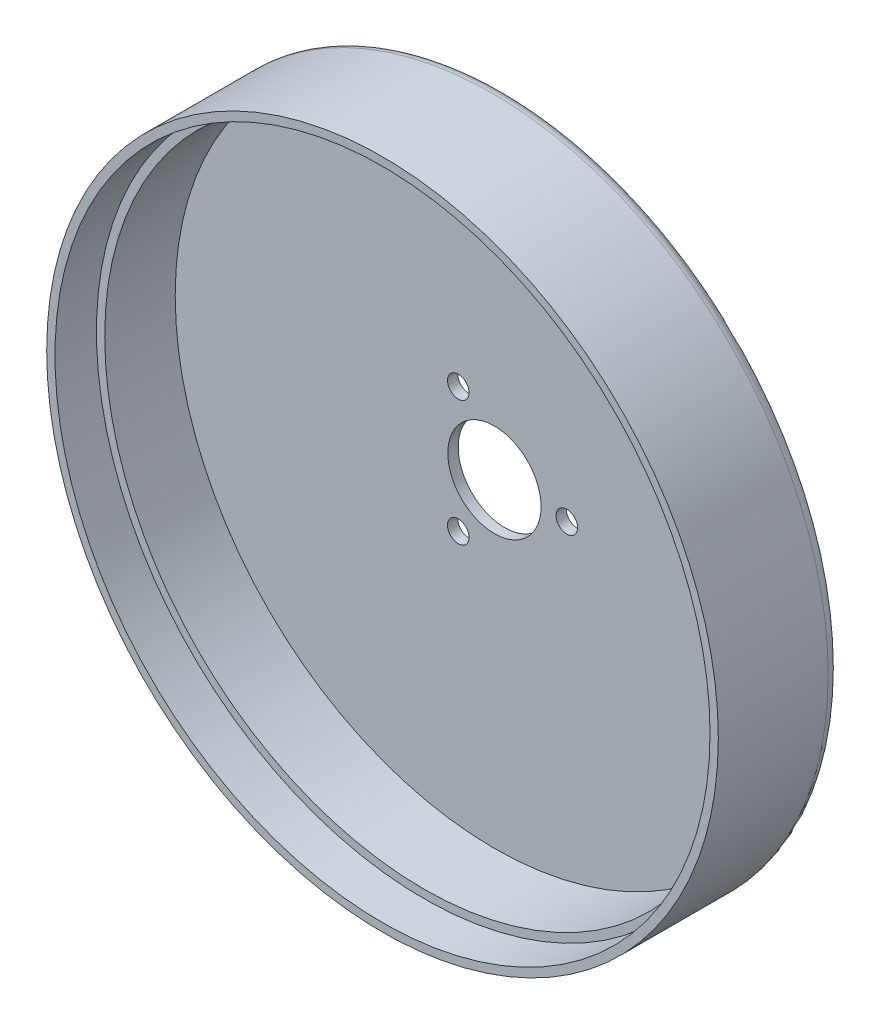
SolidWorks part; units mm, degrees
ref_plane "Front Plane" through (0, 0, 0) normal (0, 0, 1) x (1, 0, 0)
ref_plane "Top Plane" through (0, 0, 0) normal (0, 1, 0) x (1, 0, 0)
ref_plane "Right Plane" through (0, 0, 0) normal (1, 0, 0) x (0, 0, -1)
sketch "Sketch1" plane through (0, 0, 0) normal (0, 0, 1) x (1, 0, 0)
  circle A0 centre (0, 0) radius 81
  dimension "D1" = 162
extrude "Boss-Extrude1" add sketch "Sketch1" along normal blind 2.5
sketch "Sketch2" plane through (0, 0, 2.5) normal (0, 0, 1) x (1, 0, 0)
  circle A0 centre (0, 0) radius 11.25
  dimension "D1" = 22.5
extrude "Cut-Extrude1" cut sketch "Sketch2" against normal through all
sketch "Sketch3" plane through (0, 0, 2.5) normal (0, 0, 1) x (1, 0, 0)
  line L0 (-104.6653, 0) -> (111.2912, 0) construction
  line L1 (0, 113.7286) -> (0, -111.4545) construction
  line L2 (-8.725, 15.1121) -> (0, 0) construction
  line L3 (0, 0) -> (-8.725, -15.1121) construction
  circle A0 centre (0, 0) radius 17.45
  circle A1 centre (17.45, 0) radius 2.6
  circle A2 centre (-8.725, 15.1121) radius 2.6
  circle A3 centre (-8.725, -15.1121) radius 2.6
  dimension "D1" = 34.9
  dimension "D4" = 5.2
  dimension "D2" = 60
  dimension "D3" = 60
extrude "Cut-Extrude2" cut sketch "Sketch3" against normal through all contours A0 A2 | A0 A2 | A0 A1 | A0 A1 | A0 A3 | A0 A3 region at (16.3124, 0, 2.5) region at (18.5179, 0, 2.5) region at (-8.1562, 14.1269, 2.5) region at (-9.2589, 16.0369, 2.5) region at (-9.2589, -16.0369, 2.5) region at (-8.1562, -14.1269, 2.5)
sketch "Sketch4" plane through (0, 0, 2.5) normal (0, 0, 1) x (1, 0, 0)
  circle A0 centre (0, 0) radius 81
  circle A1 centre (0, 0) radius 77
  dimension "D1" = 162
  dimension "D2" = 154
extrude "Boss-Extrude2" add sketch "Sketch4" along normal blind 27
sketch "Sketch5" plane through (0, 0, 29.5) normal (0, 0, 1) x (1, 0, 0)
  circle A0 centre (0, 0) radius 79
  dimension "D1" = 158
extrude "Cut-Extrude3" cut sketch "Sketch5" against normal blind 10
fillet "Fillet1" radius 3 1 edges at (81, 0, 0)
